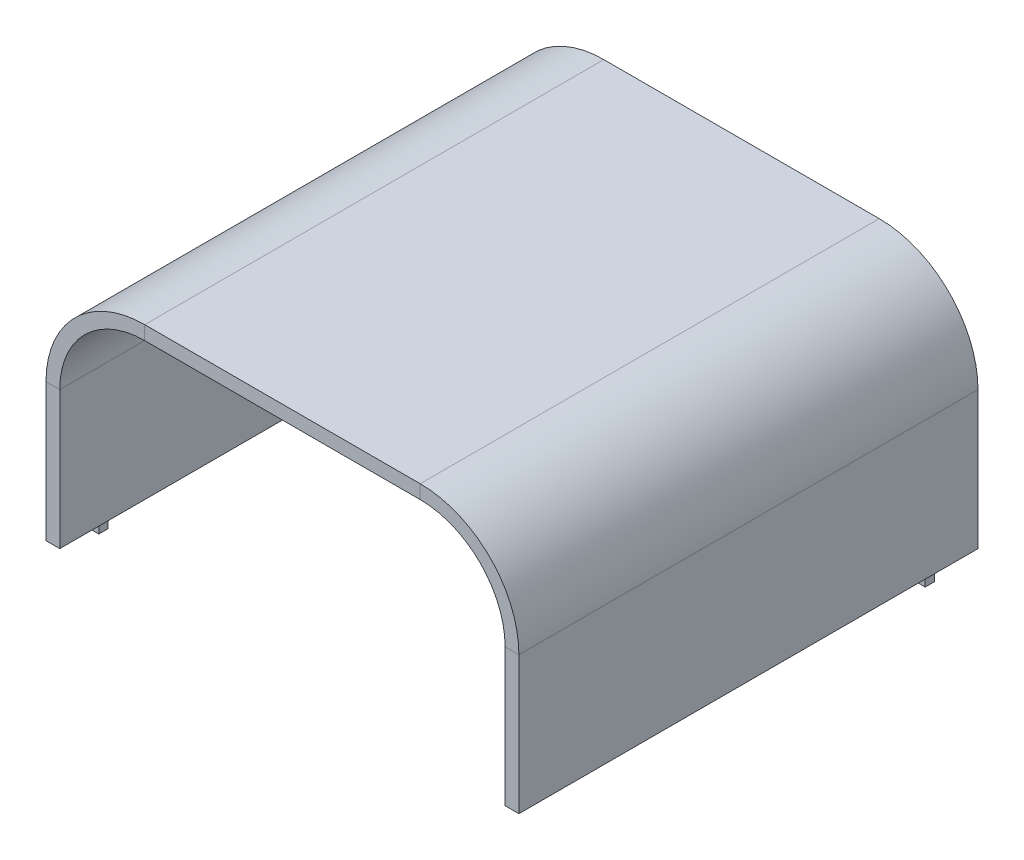
SolidWorks part; units mm, degrees
ref_plane "Front Plane" through (0, 0, 0) normal (0, 0, 1) x (1, 0, 0)
ref_plane "Top Plane" through (0, 0, 0) normal (0, 1, 0) x (1, 0, 0)
ref_plane "Right Plane" through (0, 0, 0) normal (1, 0, 0) x (0, 0, -1)
sketch "Sketch1" plane through (0, 0, 0) normal (0, 0, 1) x (1, 0, 0)
  line L0 (-250, 0) -> (250, 0) construction
  line L1 (-250, 0) -> (-250, 150)
  line L2 (-150, 250) -> (150, 250)
  line L3 (250, 150) -> (250, 0)
  arc A0 (150, 250) -> (250, 150) centre (150, 150) cw
  arc A1 (-250, 150) -> (-150, 250) centre (-150, 150) cw
  point P2 (0, 0)
  point P12 (-250, 250)
  dimension "D3" = 100
  dimension "D1" = 500
  dimension "D2" = 250
sketch "Sketch2" plane through (0, 0, 0) normal (0, 1, 0) x (1, 0, 0)
  line L1 (-257.5, -250) -> (-242.5, -250)
  line L2 (-257.5, -250) -> (-257.5, 250)
  line L3 (-257.5, 250) -> (-242.5, 250)
  line L4 (-242.5, -250) -> (-242.5, 250)
  line L5 (-257.5, -250) -> (-242.5, 250) construction
  line L6 (-257.5, 250) -> (-242.5, -250) construction
  point P0 (-250, 0)
  dimension "D1" = 500
  dimension "D2" = 15
sweep "Sweep1" add profiles "Sketch2" path "Sketch1"
sketch "Sketch3" plane through (0, 0, 0) normal (0, -1, 0) x (1, 0, 0)
  line L0 (0, 0) -> (-304.363, 0) construction
  line L1 (-250, 250) -> (-250, -250) construction
  line L2 (-257.5, 250) -> (-242.5, 250) construction
  line L3 (-242.5, -250) -> (-257.5, -250) construction
  line L4 (250, -250) -> (250, 250) construction
  line L5 (242.5, -250) -> (257.5, -250) construction
  line L6 (257.5, 250) -> (242.5, 250) construction
  line L7 (-250, 200) -> (250, 200) construction
  line L8 (-255, 205) -> (-245, 205)
  line L9 (-255, 205) -> (-255, 195)
  line L10 (-255, 195) -> (-245, 195)
  line L11 (-245, 205) -> (-245, 195)
  line L12 (-255, 205) -> (-245, 195) construction
  line L13 (-255, 195) -> (-245, 205) construction
  line L14 (245, 205) -> (255, 205)
  line L15 (245, 205) -> (245, 195)
  line L16 (245, 195) -> (255, 195)
  line L17 (255, 205) -> (255, 195)
  line L18 (245, 205) -> (255, 195) construction
  line L19 (245, 195) -> (255, 205) construction
  line L20 (245, -195) -> (255, -195)
  line L21 (245, -195) -> (245, -205)
  line L22 (245, -205) -> (255, -205)
  line L23 (255, -195) -> (255, -205)
  line L24 (245, -195) -> (255, -205) construction
  line L25 (245, -205) -> (255, -195) construction
  line L26 (-255, -195) -> (-245, -195)
  line L27 (-255, -195) -> (-255, -205)
  line L28 (-255, -205) -> (-245, -205)
  line L29 (-245, -195) -> (-245, -205)
  line L30 (-255, -195) -> (-245, -205) construction
  line L31 (-255, -205) -> (-245, -195) construction
  line L32 (250, -200) -> (-250, -200) construction
  line L33 (0, -200) -> (0, 200) construction
  point P16 (-250, 200)
  point P21 (250, 200)
  point P26 (250, -200)
  point P31 (-250, -200)
  dimension "D1" = 400
  dimension "D2" = 10
extrude "Boss-Extrude1" add sketch "Sketch3" along normal blind 10 contours L11 L8 L9 L10 | L23 L20 L21 L22 region at (-250, 0, 200) region at (250, 0, -200)
extrude "Cut-Extrude1" cut sketch "Sketch3<3>" against normal blind 10 contours L29 L26 L27 L28 | L14 L17 L16 L15 region at (-250, 0, -200)
sketch "Sketch3<3>" plane through (0, 0, 0) normal (0, -1, 0) x (1, 0, 0) same geometry as "Sketch3"
